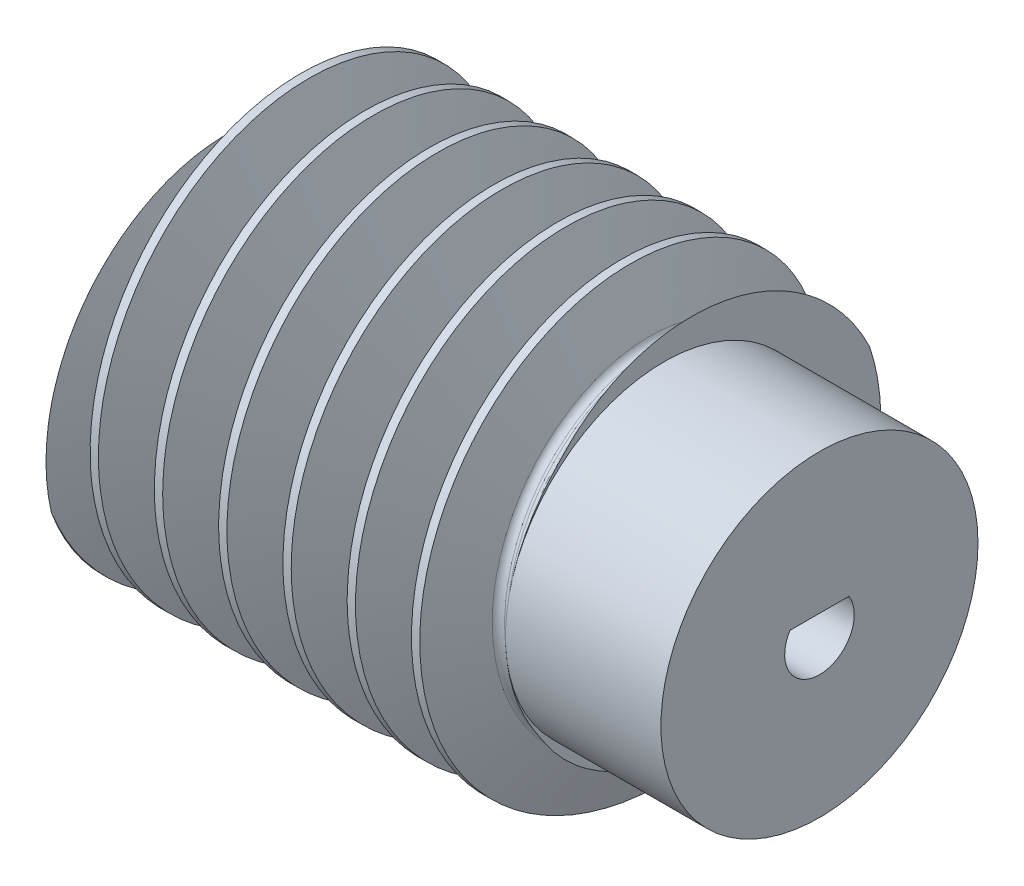
SolidWorks part; units mm, degrees
note: '?' marks a value the reader was unsure of.
ref_plane "前视基准面" through (0, 0, 0) normal (0, 0, 1) x (1, 0, 0)
ref_plane "上视基准面" through (0, 0, 0) normal (0, 1, 0) x (1, 0, 0)
ref_plane "右视基准面" through (0, 0, 0) normal (1, 0, 0) x (0, 0, -1)
ref_axis "基准轴1" through (-10.9638, 0, 0) along (1, 0, 0)?
sketch "草图1" plane through (0, 0, 0) normal (0, 0, 1) x (1, 0, 0)
  line L0 (-56.8494, 0) -> (118.6822, 0) construction
  line L1 (0, 48.1623) -> (0, -71.9241) construction
  line L2 (0, 10.6) -> (0, 0)
  line L3 (-10.9638, 0) -> (40.5935, 0) construction
  line L7 (0, 10.6) -> (20, 10.6)
  line L13 (0, 0) -> (20, 0)
  line L14 (20, 0) -> (20, 10.6)
  dimension "da1" = 10.6
  dimension "B1" = 20
revolve "旋转1" add sketch "草图1" angle 360 about L0
sketch "草图2" plane through (0, 0, 0) normal (1, 0, 0) x (0, 0, -1)
  circle A0 centre (0, 0) radius 9
  dimension "d1" = 18
sketch "草图3" plane through (0, 0, 0) normal (0, 0, 1) x (1, 0, 0)
  line L0 (0, 25.9401) -> (0, 0) construction
  line L1 (-4.1033, 10.6) -> (-1.3678, 10.6)
  line L2 (0, 10.6) -> (20, 10.6) construction
  line L3 (-1.3678, 10.6) -> (-2.3141, 8)
  line L4 (-2.6711, 7.75) -> (-2.7999, 7.75)
  line L5 (-2.7355, 10.6) -> (-2.7355, 7.75) construction
  line L6 (0, 0) -> (8.7963, 0) construction
  line L7 (-3.5209, 9) -> (-1.9501, 9) construction
  line L8 (-3.1569, 8) -> (-4.1033, 10.6)
  line L9 (-4.1033, 10.6) -> (-4.1033, -9.4) construction
  line L10 (-2.7355, 10.6) -> (0, 10.6) construction
  arc A0 (-3.1569, 8) -> (-2.7999, 7.75) centre (-2.7999, 8.13) ccw
  arc A1 (-2.6711, 7.75) -> (-2.3141, 8) centre (-2.6711, 8.13) ccw
  point P14 (-3.0659, 7.75)
  point P19 (-2.4051, 7.75)
  dimension "ppn" = 0.38
  dimension "df1" = 15.5
  dimension "d1" = 18
  dimension "0.5px" = 1.5708
  dimension "aa1" = 20
  dimension "aa" = 20
sketch "草图4" plane through (0, 0, 0) normal (1, 0, 0) x (0, 0, -1)
  circle A0 centre (0, 0) radius 7.75
sketch "草图5" plane through (20, 0, 0) normal (1, 0, 0) x (0, 0, -1)
  circle A0 centre (0, 0) radius 7.75 construction
  circle A1 centre (0, 0) radius 7.75
curve "螺旋线/涡状线1" pitch 3.1416 height 30.4 turns 9.6766
sweep "切除-扫描1" cut profiles "草图3" path "螺旋线/涡状线1"
extrude "凸台-拉伸2" add sketch "草图5" along normal blind 7.6
sketch "草图6" plane through (27.6, 0, 0) normal (1, 0, 0) x (0, 0, -1)
  line L0 (-1.4422, 0.9) -> (1.4422, 0.9)
  line L1 (-14.3074, -1.7) -> (14.3074, -1.7) construction
  arc A0 (-1.4422, 0.9) -> (1.4422, 0.9) centre (0, 0) ccw
  point P8 (0, -1.7)
  dimension "D1" = 3.4
  dimension "D2" = 2.6
extrude "切除-拉伸1" cut sketch "草图6" against normal blind 20
